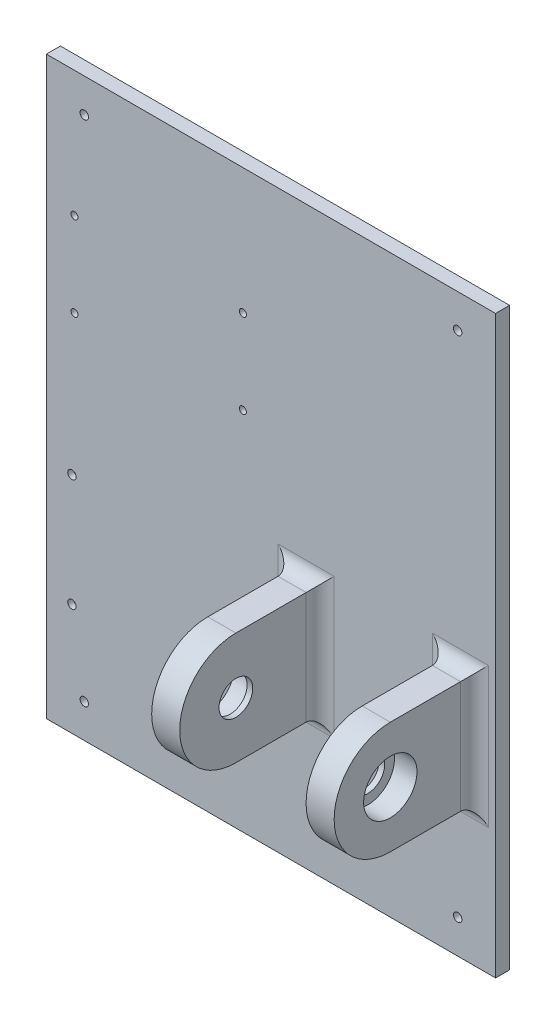
SolidWorks part; units mm, degrees
ref_plane "正面" through (0, 0, 0) normal (0, 0, 1) x (1, 0, 0)
ref_plane "平面" through (0, 0, 0) normal (0, 1, 0) x (1, 0, 0)
ref_plane "右側面" through (0, 0, 0) normal (1, 0, 0) x (0, 0, -1)
sketch "ｽｹｯﾁ2" plane through (0, 0, 0) normal (0, 0, 1) x (1, 0, 0)
  line L0 (-120, 124.8362) -> (-120, -80.1638)
  line L5 (-120, -80.1638) -> (40, -80.1638)
  line L6 (40, -80.1638) -> (40, 124.8362)
  line L7 (40, 124.8362) -> (-120, 124.8362)
  point P0 (0, 0)
  dimension "D1" = 205
  dimension "D2" = 120
  dimension "D3" = 40
extrude "ﾎﾞｽ - 押し出し1" add sketch "ｽｹｯﾁ2" along normal blind 5
sketch "ｽｹｯﾁ3" plane through (0, 0, 0) normal (0, 0, 1) x (1, 0, 0)
  line L0 (-32.5, 10) -> (-32.5, -30)
  line L1 (-32.5, -30) -> (-22.5, -30)
  line L2 (-22.5, -30) -> (-22.5, 10)
  line L3 (-22.5, 10) -> (-32.5, 10)
  dimension "D1" = 10
  dimension "D2" = 40
  dimension "D3" = 30
  dimension "D4" = 22.5
extrude "ﾎﾞｽ - 押し出し2" add sketch "ｽｹｯﾁ3" along normal blind 35
ref_plane "平面1" through (-32.5, 0, 0) normal (-1, 0, 0) x (0, 0, 1)
sketch "ｽｹｯﾁ4" plane through (-32.5, 0, 0) normal (-1, 0, 0) x (0, 0, 1)
  line L0 (35, 10) -> (35, -30) construction
  circle A0 centre (35, -10) radius 20
extrude "ﾎﾞｽ - 押し出し3" add sketch "ｽｹｯﾁ4" against normal blind 10
sketch "ｽｹｯﾁ5" plane through (-32.5, 0, 0) normal (-1, 0, 0) x (0, 0, 1)
  circle A0 centre (35, -10) radius 9.5
  dimension "D1" = 19
extrude "ｶｯﾄ - 押し出し1" cut sketch "ｽｹｯﾁ5" against normal blind 8
sketch "ｽｹｯﾁ13" plane through (-22.5, 0, 0) normal (1, 0, 0) x (0, 0, -1)
  circle A0 centre (-35, -10) radius 6
  dimension "D1" = 12
extrude "ｶｯﾄ - 押し出し2" cut sketch "ｽｹｯﾁ13" against normal through all
fillet "ﾌｨﾚｯﾄ1" radius 5 4 edges at (-27.5, -30, 5) (-32.5, -10, 5) (-27.5, 10, 5) (-22.5, -10, 5)
mirror "ﾐﾗｰ2" about plane through (0, 0, 0) normal (1, 0, 0) of "ﾌｨﾚｯﾄ1", "ｶｯﾄ - 押し出し2", "ｶｯﾄ - 押し出し1", "ﾎﾞｽ - 押し出し3", "ﾎﾞｽ - 押し出し2"
ref_plane "平面2" through (-22.5, 0, 0) normal (1, 0, 0) x (0, 0, -1)
sketch "ｽｹｯﾁ14" plane through (0, 0, 0) normal (0, 0, 1) x (1, 0, 0)
  circle A0 centre (-110.9, -0.35) radius 1.5
  circle A1 centre (-110.9, -40.35) radius 1.5
  dimension "D1" = 3
  dimension "D2" = 3
  dimension "D3" = 110.9
  dimension "D5" = 110.9
  dimension "D4" = 40
  dimension "D6" = 0.35
extrude "ｶｯﾄ - 押し出し3" cut sketch "ｽｹｯﾁ14" along normal blind 10
sketch "ｽｹｯﾁ15" plane through (0, 0, 0) normal (0, 0, 1) x (1, 0, 0)
  line L0 (-110.9, -0.35) -> (-110.9, -40.35) construction
  line L2 (-113.75, -1.9954) -> (-110.9, -3.6409)
  line L3 (-110.9, -3.6409) -> (-108.05, -1.9954)
  line L4 (-108.05, -1.9954) -> (-108.05, 1.2954)
  line L5 (-108.05, 1.2954) -> (-110.9, 2.9409)
  line L6 (-110.9, 2.9409) -> (-113.75, 1.2954)
  line L7 (-113.75, 1.2954) -> (-113.75, -1.9954)
  line L8 (-113.75, -41.9954) -> (-110.9, -43.6409)
  line L9 (-110.9, -43.6409) -> (-108.05, -41.9954)
  line L10 (-108.05, -41.9954) -> (-108.05, -38.7046)
  line L11 (-108.05, -38.7046) -> (-110.9, -37.0591)
  line L12 (-110.9, -37.0591) -> (-113.75, -38.7046)
  line L13 (-113.75, -38.7046) -> (-113.75, -41.9954)
  circle A0 centre (-110.9, -0.35) radius 3.381
  circle A1 centre (-110.9, -40.35) radius 2.85
  circle A2 centre (-110.9, -0.35) radius 2.85 construction
  circle A3 centre (-110.9, -40.35) radius 2.85 construction
  dimension "D1" = 5.7
  dimension "D2" = 5.7
  dimension "D3" = 5.7
extrude "ｶｯﾄ - 押し出し4" cut sketch "ｽｹｯﾁ15" along normal blind 3 contours A1 | L2 L3 L4 L5 L6 L7 | L8 L9 L10 L11 L12 L13
sketch "ｽｹｯﾁ16" plane through (0, 0, 5) normal (0, 0, 1) x (1, 0, 0)
  line L0 (-120, -80.1638) -> (-120, -50.1638)
  line L1 (-120, 124.8362) -> (-120, -80.1638) construction
  line L2 (-120, -50.1638) -> (40, -50.1638)
  line L3 (40, -80.1638) -> (40, 124.8362) construction
  line L4 (40, -50.1638) -> (40, -80.1638)
  line L5 (40, -80.1638) -> (-120, -80.1638)
  dimension "D1" = 30
sketch "ｽｹｯﾁ17" plane through (0, 0, 5) normal (0, 0, 1) x (1, 0, 0)
  line L0 (-106.5, 112.8362) -> (-106.5, -68.1638)
  line L1 (-106.5, -68.1638) -> (26.5, -68.1638)
  line L2 (26.5, -68.1638) -> (26.5, 112.8362)
  line L3 (26.5, 112.8362) -> (-106.5, 112.8362)
  line L4 (40, 124.8362) -> (-120, 124.8362) construction
  line L5 (-120, 124.8362) -> (-120, -80.1638) construction
  dimension "D1" = 133
  dimension "D2" = 181
  dimension "D3" = 12
  dimension "D4" = 13.5
sketch "ｽｹｯﾁ18" plane through (0, 0, 5) normal (0, 0, 1) x (1, 0, 0)
  circle A0 centre (-106.5, 112.8362) radius 1.5
  circle A1 centre (-106.5, -68.1638) radius 1.5
  circle A2 centre (26.5, -68.1638) radius 1.5
  circle A3 centre (26.5, 112.8362) radius 1.5
  dimension "D1" = 3
  dimension "D2" = 3
  dimension "D3" = 3
  dimension "D4" = 3
extrude "ｶｯﾄ - 押し出し5" cut sketch "ｽｹｯﾁ18" against normal through all both contours A1 | A2 | A0 | A3
hole_wizard "M3x0.5 ねじ穴1" positions "ｽｹｯﾁ19" profile "ｽｹｯﾁ20" tap size "M3x0.5" standard "JIS" end condition through all
sketch "ｽｹｯﾁ19" plane through (0, 0, 5) normal (0, 0, 1) x (1, 0, 0)
  point P0 (-110, 80)
  point P2 (-50, 80)
  dimension "D1" = 60
  dimension "D2" = 80
  dimension "D3" = 50
sketch "ｽｹｯﾁ20" plane through (-110, 80, 5) normal (1, 0, 0) x (0, -1, 0)
  line L0 (0, 0) -> (0, 5)
  line L1 (0, 5) -> (1.25, 5)
  line L2 (1.25, 5) -> (1.25, 0)
  line L5 (1.25, 0) -> (0, 0)
  line L11 (0, -6.35) -> (0, 107.95) construction
  dimension "次ｻｰﾌｪｽまでのねじ下穴ﾄﾞﾘﾙ直径" = 2.5
  dimension "次ｻｰﾌｪｽまでのねじ下穴ﾄﾞﾘﾙの深さ" = 5
cosmetic thread "穴のねじ山1" parameters "D2"=3
cosmetic thread "穴のねじ山2" parameters "D2"=3
hole_wizard "M3x0.5 ねじ穴2" positions "ｽｹｯﾁ21" profile "ｽｹｯﾁ22" tap size "M3x0.5" standard "JIS" end condition through all
sketch "ｽｹｯﾁ21" plane through (0, 0, 5) normal (0, 0, 1) x (1, 0, 0)
  point P0 (-110, 50)
  point P2 (-50, 50)
  dimension "D1" = 50
  dimension "D2" = 60
  dimension "D3" = 50
  dimension "D4" = 50
sketch "ｽｹｯﾁ22" plane through (-110, 50, 5) normal (1, 0, 0) x (0, -1, 0)
  line L0 (0, 0) -> (0, 5)
  line L1 (0, 5) -> (1.25, 5)
  line L2 (1.25, 5) -> (1.25, 0)
  line L5 (1.25, 0) -> (0, 0)
  line L11 (0, -6.35) -> (0, 107.95) construction
  dimension "次ｻｰﾌｪｽまでのねじ下穴ﾄﾞﾘﾙ直径" = 2.5
  dimension "次ｻｰﾌｪｽまでのねじ下穴ﾄﾞﾘﾙの深さ" = 5
cosmetic thread "穴のねじ山3" parameters "D2"=3
cosmetic thread "穴のねじ山4" parameters "D2"=3
equation "\"D5@ｽｹｯﾁ14\"=\"D3@ｽｹｯﾁ14\""
